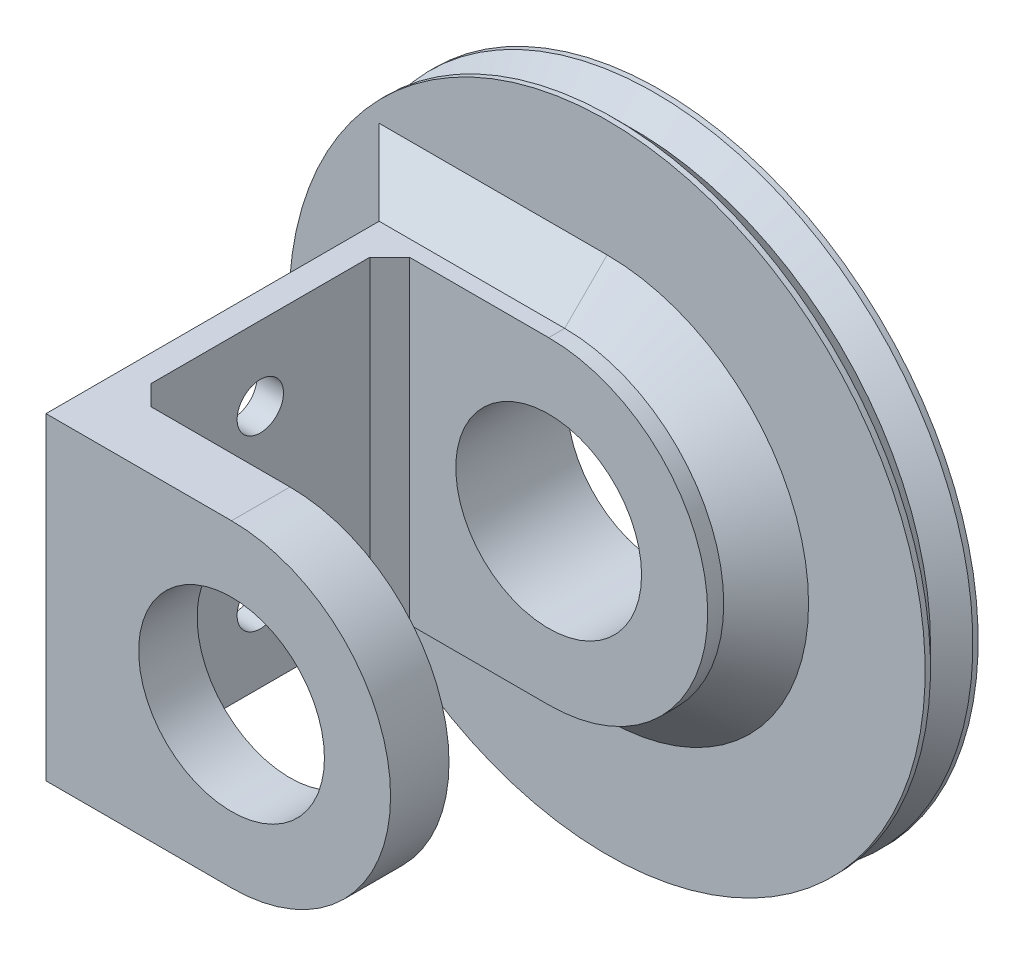
SolidWorks part; units mm, degrees
ref_plane "Front Plane" through (0, 0, 0) normal (0, 0, 1) x (1, 0, 0)
ref_plane "Top Plane" through (0, 0, 0) normal (0, 1, 0) x (1, 0, 0)
ref_plane "Right Plane" through (0, 0, 0) normal (1, 0, 0) x (0, 0, -1)
sketch "Sketch2" plane through (0, 0, 0) normal (0, 0, 1) x (1, 0, 0)
  circle A0 centre (0, 0) radius 10.9982
  dimension "D1" = 21.9964
sketch "Sketch4" plane through (0, 0, 0) normal (0, 0, 1) x (1, 0, 0)
  line L0 (-19.05, 19.05) -> (-19.05, -19.05) construction
  line L1 (-19.05, 19.05) -> (0, 19.05)
  line L2 (-19.05, -19.05) -> (0, -19.05)
  line L3 (-19.05, 19.05) -> (-22.225, 19.05)
  line L4 (-22.225, 19.05) -> (-22.225, -19.05)
  line L5 (-22.225, -19.05) -> (-19.05, -19.05)
  arc A0 (0, -19.05) -> (0, 19.05) centre (0, 0) ccw
  circle A1 centre (0, 0) radius 11.127
  dimension "D1" = 38.1
  dimension "D2" = 22.254
  dimension "D3" = 3.175
extrude "Boss-Extrude1" add sketch "Sketch4" against normal blind 7
extrude "Cut-Extrude1" [suppressed] cut sketch "Sketch2" against normal mid plane 25.4 contours A0
sketch "Sketch6" plane through (0, 0, 0) normal (0, 0, 1) x (1, 0, 0)
  line L0 (-22.225, -19.05) -> (0, -19.05) construction
  line L1 (-22.225, -19.05) -> (-19.05, -19.05)
  line L2 (-22.225, -19.05) -> (-22.225, 19.05)
  line L3 (-22.225, 19.05) -> (-19.05, 19.05)
  line L4 (-19.05, -19.05) -> (-19.05, 19.05)
  line L5 (-22.225, 19.05) -> (-22.225, -19.05) construction
  line L6 (0, 19.05) -> (-22.225, 19.05) construction
  line L7 (-19.05, 19.05) -> (-19.05, -19.05) construction
extrude "Boss-Extrude2" add sketch "Sketch6" along normal blind 15.494
chamfer "Chamfer1" distance 2.38 angle 45 1 edges at (-19.05, 0, 0)
mirror "Mirror1" about plane through (0, 0, 15.494) normal (0, 0, -1) of bodies 103
sketch "Sketch8" plane through (-19.05, 0, 0) normal (1, 0, 0) x (0, 0, -1)
  line L0 (-15.494, 19.05) -> (-15.494, -19.05) construction
  line L1 (-28.608, 19.05) -> (-2.38, 19.05) construction
  line L2 (-28.608, -19.05) -> (-2.38, -19.05) construction
  line L3 (-15.494, 0) -> (-5.0615, 0) construction
  circle A0 centre (-15.494, 10.16) radius 2.7781
  circle A1 centre (-15.494, -10.16) radius 2.7781
  dimension "D1" = 5.5562
  dimension "D2" = 10.16
extrude "Cut-Extrude2" cut sketch "Sketch8" against normal through all
sketch "Sketch9" plane through (0, 0, -7) normal (0, 0, -1) x (-1, 0, 0)
  circle A0 centre (0, 0) radius 11.127 construction
  circle A1 centre (0, 0) radius 11.127
  circle A2 centre (0, 0) radius 38.1
  dimension "D1" = 76.2
extrude "Boss-Extrude3" add sketch "Sketch9" along normal blind 3.175 separate body
chamfer "Chamfer2" distance 2.54 angle 45 1 edges at (-38.1, 0, -10.175)
mirror "Mirror2" about plane through (0, 0, -10.175) normal (0, 0, -1) of bodies 106
combine bodies "Combine1" operation type add bodies to combine 105 107
chamfer "Chamfer3" distance 5.08 angle 45 4 edges at (-22.225, 0, -7) (-11.1125, -19.05, -7) (-11.1125, 19.05, -7) (19.05, 0, -7)
